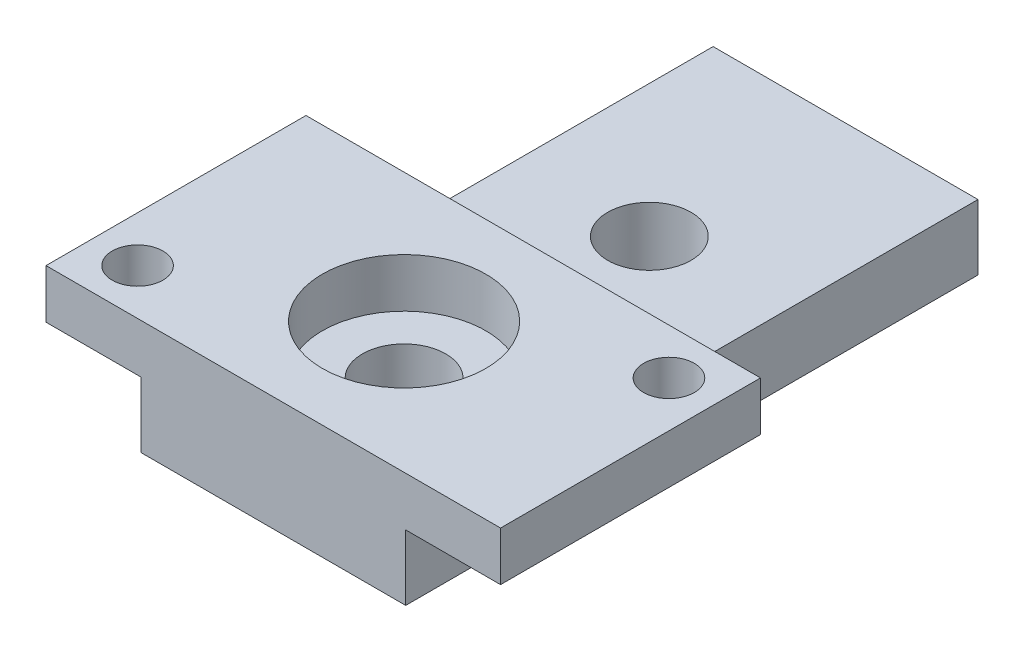
SolidWorks part; units mm, degrees
ref_plane "Front Plane" through (0, 0, 0) normal (0, 0, 1) x (1, 0, 0)
ref_plane "Top Plane" through (0, 0, 0) normal (0, 1, 0) x (1, 0, 0)
ref_plane "Right Plane" through (0, 0, 0) normal (1, 0, 0) x (0, 0, -1)
sketch "Sketch1" plane through (0, 0, 0) normal (0, 1, 0) x (1, 0, 0)
  line L1 (0, 0) -> (27.8, 0)
  line L2 (0, 0) -> (0, 15.9)
  line L3 (0, 15.9) -> (27.8, 15.9)
  line L4 (27.8, 0) -> (27.8, 15.9)
  circle A0 centre (2.8, 2.8) radius 1.55
  circle A1 centre (25, 13.1) radius 1.55
  dimension "D3" = 3.1
  dimension "D1" = 27.8
  dimension "D2" = 15.9
  dimension "D4" = 2.8
  dimension "D5" = 2.8
  dimension "D6" = 2.8
  dimension "D7" = 2.8
extrude "Boss-Extrude1" add sketch "Sketch1" along normal blind 3
sketch "Sketch2" plane through (0, 0, 0) normal (0, -1, 0) x (1, 0, 0)
  line L0 (0, 0) -> (27.8, 0) construction
  line L1 (5.8, 0) -> (22, 0)
  line L2 (5.8, 0) -> (5.8, -35)
  line L3 (5.8, -35) -> (22, -35)
  line L4 (22, 0) -> (22, -35)
  circle A0 centre (2.8, -2.8) radius 1.55 construction
  circle A1 centre (25, -13.1) radius 1.55 construction
  dimension "D1" = 3
  dimension "D2" = 3
  dimension "D3" = 35
extrude "Boss-Extrude2" add sketch "Sketch2" along normal blind 4
sketch "Sketch3" plane through (0, -4, 0) normal (0, -1, 0) x (1, 0, 0)
  line L0 (22, 0) -> (5.8, 0) construction
  line L1 (13.9, -8) -> (13.9, -23) construction
  line L2 (5.8, 0) -> (5.8, -35) construction
  line L3 (22, -35) -> (22, 0) construction
  circle A0 centre (13.9, -8) radius 2.55
  circle A1 centre (13.9, -23) radius 2.55
  dimension "D1" = 5.1
  dimension "D2" = 8
  dimension "D3" = 15
extrude "Cut-Extrude1" cut sketch "Sketch3" against normal blind 4
sketch "Sketch4" plane through (0, 3, 0) normal (0, 1, 0) x (1, 0, 0)
  circle A0 centre (13.9, 8) radius 2.55 construction
  circle A2 centre (13.9, 8) radius 2.55
  circle A5 centre (13.9, 8) radius 5
  point P9 (14.2375, 23)
  point P11 (0, 0)
  dimension "D1" = 10
extrude "Cut-Extrude4" cut sketch "Sketch4" against normal blind 3 contours A5 A2 | A2 region at (13.9, 3, -8) region at (9.0414, 3, -8)
